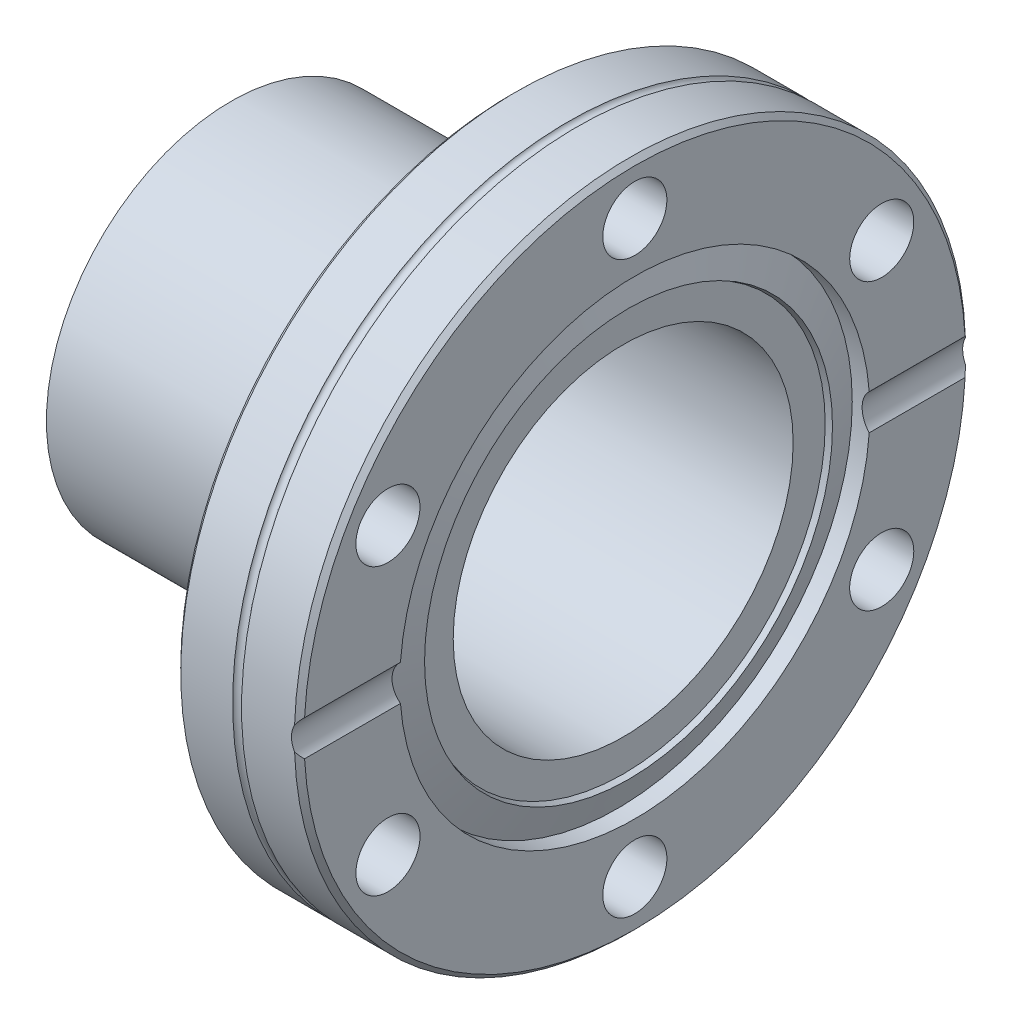
SolidWorks part; units mm, degrees
material "AISI 304"
ref_plane "Спереди" through (0, 0, 0) normal (0, 0, 1) x (1, 0, 0)
ref_plane "Сверху" through (0, 0, 0) normal (0, 1, 0) x (1, 0, 0)
ref_plane "Справа" through (0, 0, 0) normal (1, 0, 0) x (0, 0, -1)
ref_axis "Ось1" through (-110.1507, 0, 0) along (1, 0, 0)
sketch "Эскиз1" plane through (0, 0, 0) normal (0, 0, 1) x (1, 0, 0)
  line L0 (0, 78.5612) -> (0, 0) construction
  line L1 (0, 0) -> (-13.1, 0) construction
  line L2 (-12.6, 34.55) -> (-7.2583, 34.55)
  line L3 (-0.4, 34.05) -> (-0.4, 24.2)
  line L4 (-0.4, 24.2) -> (-2.2147, 24.2)
  line L5 (-2.2147, 24.2) -> (-1.05, 21)
  line L6 (-1.05, 21) -> (-1.6, 20.7998)
  line L7 (-1.6, 20.7998) -> (-1.6, 17.5)
  line L10 (-9.1401, 34.25) -> (-3.4435, 34.25) construction
  line L11 (-13.1, 19) -> (-63.4, 19)
  line L12 (-6.3417, 34.55) -> (-0.9, 34.55)
  line L13 (-13.1, 34.05) -> (-12.6, 34.55)
  line L14 (-0.9, 34.55) -> (-0.4, 34.05)
  line L15 (-13.1, 29.35) -> (-0.4, 29.35) construction
  line L16 (-63.4, 19) -> (-63.4, 17.5)
  line L17 (-63.4, 17.5) -> (-1.6, 17.5)
  line L18 (-13.1, 19) -> (-13.1, 34.05)
  arc A0 (-7.2583, 34.55) -> (-6.3417, 34.55) centre (-6.8, 34.75) ccw
  point P5 (-0.4, 34.55)
  dimension "D2" = 0.5
  dimension "D1" = 69.1
  dimension "D3" = 6.4
  dimension "D4" = 0.3
  dimension "D5" = 12.7
  dimension "D6" = 2.1
  dimension "D7" = 45
  dimension "D8" = 20
  dimension "D9" = 48.4
  dimension "D10" = 0.65
  dimension "D11" = 42
  dimension "D12" = 1.2
  dimension "D13" = 63
  dimension "D14" = 38
  dimension "D15" = 1.5
  dimension "D16" = 0.5
  dimension "D17" = 45
  dimension "D21" = 58.7
revolve "Повернуть2" add sketch "Эскиз1" angle 360 about L1 region at (-9.9291, 33.8973, 0)
hole_wizard "Отверстие с зазором M61" positions "Эскиз3" profile "Эскиз2" hole size "M6" standard "DIN" end condition through all
sketch "Эскиз3" plane through (-0.4, 0, 0) normal (1, 0, 0) x (0, 0, -1)
  point P0 (0, 29.35)
sketch "Эскиз2" plane through (-0.4, 29.35, 0) normal (0, 1, 0) x (0, 0, -1)
  line L0 (0, 0) -> (0, 63)
  line L1 (0, 63) -> (3.3, 63)
  line L2 (3.3, 63) -> (3.3, 0)
  line L5 (3.3, 0) -> (0, 0)
  line L11 (0, -6.35) -> (0, 107.95) construction
  dimension "Диаметр сквозного отверстия" = 6.6
  dimension "Глубина сквозного отверстия" = 63
pattern_circular "Круговой массив3" count 6 over 360 about axis through (-110.1507, 0, 0) along (1, 0, 0) of "Отверстие с зазором M61"
ref_plane "Плоскость1" through (0, 0, -34.55) normal (0, 0, -1) x (-1, 0, 0)
sketch "Эскиз6" plane through (0, 0, -34.55) normal (0, 0, -1) x (-1, 0, 0)
  line L0 (-31.7828, 0) -> (1.2, 0) construction
  line L1 (0.4, 34.05) -> (0.4, 24.2) construction
  circle A0 centre (-1.3, 0) radius 2.5
  dimension "D1" = 5
  dimension "D2" = 0.8
extrude "Вырез-Вытянуть1" cut sketch "Эскиз6" against normal blind 12
pattern_circular "Круговой массив2" count 2 over 360 about axis through (-110.1507, 0, 0) along (1, 0, 0) of "Вырез-Вытянуть1"
sketch "Эскиз7" plane through (0, 0, 0) normal (0, 0, 1) x (1, 0, 0)
  line L0 (-63.4, 17.5) -> (-1.6, 17.5) construction
  line L1 (-13.1, 19) -> (-63.4, 19) construction
  line L2 (-63.4, 19) -> (-63.4, 17.5) construction
  line L3 (-63.4, 17.5) -> (-41.98, 17.5)
  line L4 (-41.98, 19) -> (-63.4, 19)
  line L5 (-63.4, 19) -> (-63.4, 17.5)
  line L6 (-41.98, 19) -> (-41.98, 17.5)
  line L7 (0, 0) -> (-79.3777, 0) construction
  line L8 (-0.4, 34.05) -> (-0.4, 24.2) construction
  dimension "D1" = 41.58
revolve "Вырез-Повернуть1" cut sketch "Эскиз7" angle 360 about L7
